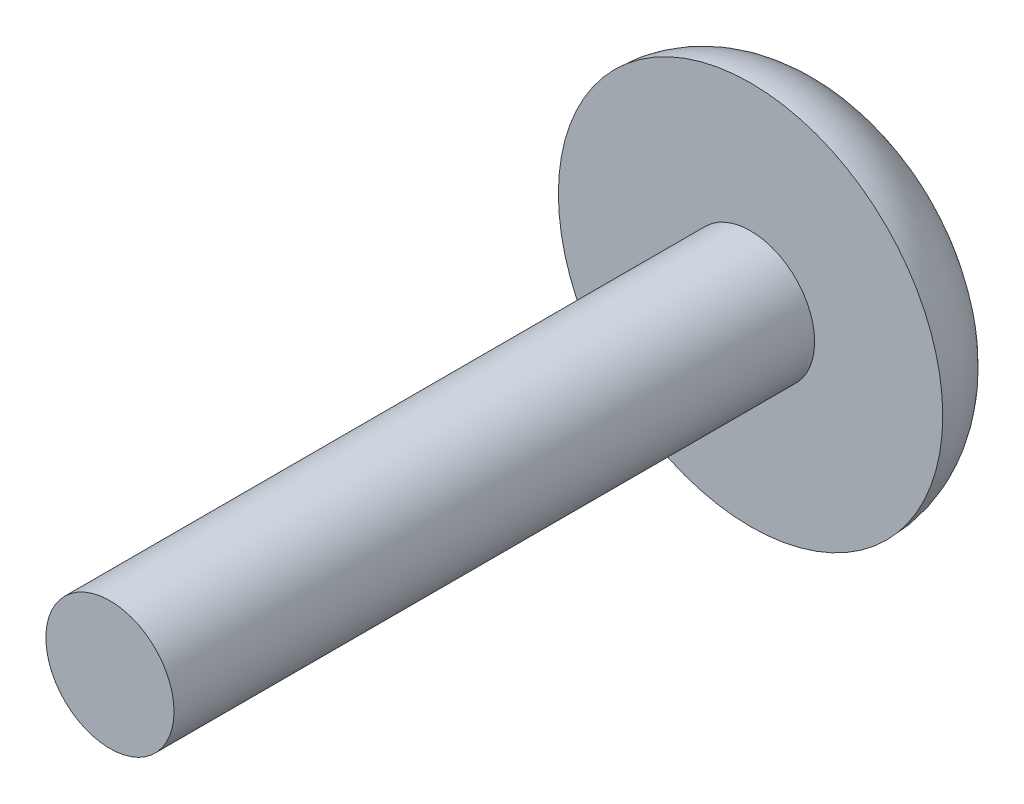
SolidWorks part; units mm, degrees
ref_plane "Front Plane" through (0, 0, 0) normal (0, 0, 1) x (1, 0, 0)
ref_plane "Top Plane" through (0, 0, 0) normal (0, 1, 0) x (1, 0, 0)
ref_plane "Right Plane" through (0, 0, 0) normal (1, 0, 0) x (0, 0, -1)
sketch "Sketch1" plane through (0, 0, 0) normal (0, 0, 1) x (1, 0, 0)
  circle A0 centre (0, 0) radius 4.5
  dimension "D1" = 9
extrude "Boss-Extrude1" add sketch "Sketch1" along normal blind 2
fillet "Fillet1" radius 2 1 edges at (4.5, 0, 0)
sketch "Sketch2" plane through (0, 0, 0) normal (0, 0, -1) x (-1, 0, 0)
  line L0 (0.2308, -0.25) -> (0.2308, -1.45)
  line L1 (0.2308, 1.45) -> (-0.2308, 1.45)
  line L2 (0.2308, 1.45) -> (0.2308, 0.25)
  line L3 (0.2308, -1.45) -> (-0.2692, -1.45)
  line L4 (-0.2308, 1.45) -> (-0.2308, 0.25)
  line L6 (-0.2308, -0.25) -> (-0.2692, -1.45)
  line L7 (-1.4308, -0.25) -> (-0.2308, -0.25)
  line L8 (-1.4308, -0.25) -> (-1.4308, 0.25)
  line L9 (-1.4308, 0.25) -> (-0.2308, 0.25)
  line L10 (1.4308, -0.25) -> (1.4308, 0.25)
  line L11 (-1.4308, -0.25) -> (-0.2308, -0.0437) construction
  line L12 (-1.4308, 0.25) -> (-0.2308, 0.0426) construction
  line L13 (0.2308, -0.25) -> (1.4308, -0.25)
  line L16 (0.2308, 0.25) -> (1.4308, 0.25)
  point P0 (0, 0)
  point P6 (0.0193, -0.0007)
  dimension "D1" = 0.5
  dimension "D2" = 0.5
  dimension "D3" = 1.2
  dimension "D4" = 1.2
  dimension "D5" = 1.2
  dimension "D6" = 1.2
extrude "Cut-Extrude1" cut sketch "Sketch2" against normal blind 0.5
sketch "Sketch3" plane through (0, 0, 2) normal (0, 0, 1) x (1, 0, 0)
  circle A0 centre (0, 0) radius 1.5
  dimension "D1" = 3
extrude "Boss-Extrude2" add sketch "Sketch3" along normal blind 15
